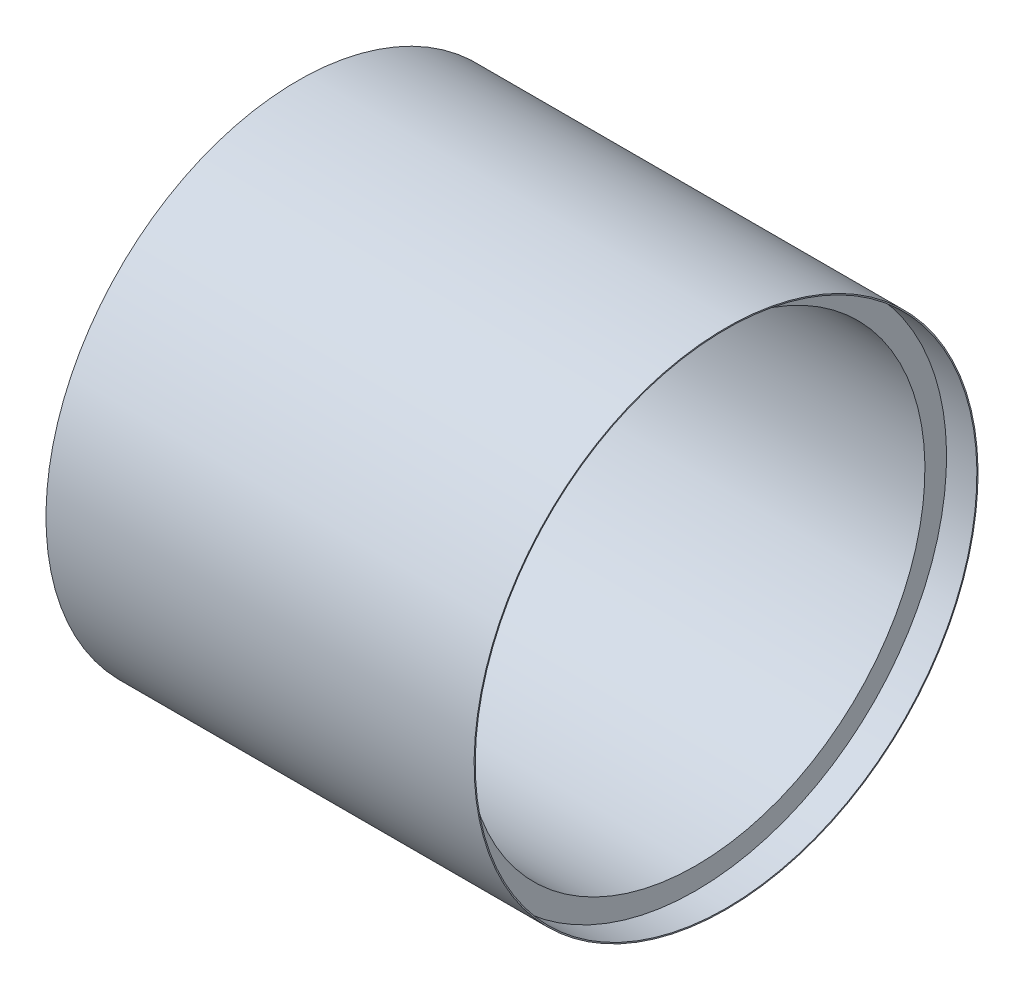
SolidWorks part; units mm, degrees
material "Carbon sandwich"
ref_plane "Front" through (0, 0, 0) normal (0, 0, 1) x (1, 0, 0)
ref_plane "Top" through (0, 0, 0) normal (0, 1, 0) x (1, 0, 0)
ref_plane "Right" through (0, 0, 0) normal (1, 0, 0) x (0, 0, -1)
sketch "Sketch1" plane through (0, 0, 0) normal (0, 0, 1) x (1, 0, 0)
  line L0 (39.1463, 83.9724) -> (49.3063, 83.9724)
  line L1 (49.3063, 83.9724) -> (49.3063, 76.7334)
  line L2 (49.3063, 76.7334) -> (172.3185, 76.7334)
  line L3 (172.3185, 76.7334) -> (172.3185, 83.9724)
  line L4 (172.3185, 83.9724) -> (182.4785, 83.9724)
  line L5 (182.4785, 83.9724) -> (182.4785, 84.3534)
  line L6 (182.4785, 84.3534) -> (39.1463, 84.3534)
  line L7 (39.1463, 84.3534) -> (39.1463, 83.9724)
  line L8 (0, 0) -> (134.0356, 0) construction
  dimension "D1" = 76.7334
  dimension "D2" = 0.381
  dimension "D3" = 10.16
  dimension "D4" = 10.16
  dimension "D5" = 123.0122
  dimension "D6" = 84.3534
  dimension "D7" = 0.381
revolve "Revolve1" add sketch "Sketch1" angle 360 about L8 region at (110.8124, 80.573, 0)
